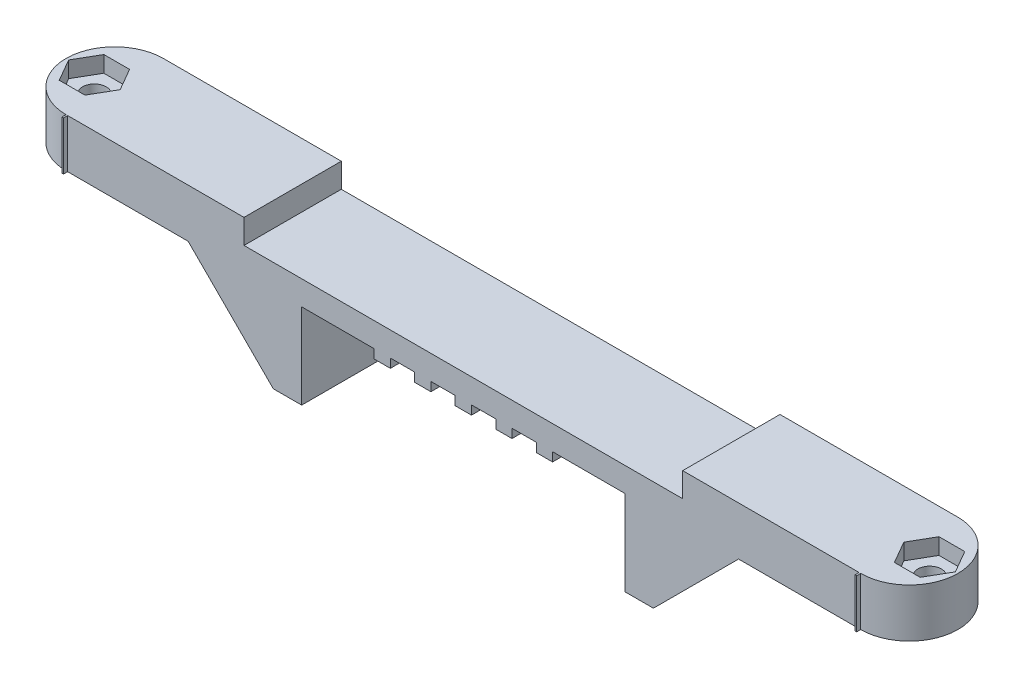
SolidWorks part; units mm, degrees
ref_plane "Front Plane" through (0, 0, 0) normal (0, 0, 1) x (1, 0, 0)
ref_plane "Top Plane" through (0, 0, 0) normal (0, 1, 0) x (1, 0, 0)
ref_plane "Right Plane" through (0, 0, 0) normal (1, 0, 0) x (0, 0, -1)
sketch "Sketch1" plane through (0, 0, 0) normal (0, 1, 0) x (1, 0, 0)
  line L0 (-49, 0) -> (49, 0) construction
  line L1 (-49, 6) -> (49, 6)
  line L2 (-49, -6) -> (49, -6)
  arc A0 (-49, 6) -> (-49, -6) centre (-49, 0) ccw
  arc A1 (49, -6) -> (49, 6) centre (49, 0) ccw
  circle A2 centre (-51.5, 0) radius 1.45
  circle A3 centre (51.5, 0) radius 1.45
  point P2 (0, 0)
  point P12 (-55, 0)
  point P13 (55, 0)
  dimension "D3" = 2.9
  dimension "D4" = 3.5
  dimension "D1" = 110
  dimension "D2" = 12
  dimension "D5" = 3.5
extrude "Boss-Extrude1" add sketch "Sketch1" along normal blind 3 contours L2 A1 L1 A0 | A2 | A3
sketch "Sketch4" plane through (0, 0, 0) normal (0, -1, 0) x (1, 0, 0)
  line L0 (-19.94, 6) -> (-19.94, -6)
  line L1 (-49, 6) -> (49, 6) construction
  line L2 (-49, -6) -> (49, -6) construction
  line L3 (-19.94, -6) -> (-23.44, -6)
  line L4 (-23.44, -6) -> (-23.44, 6)
  line L5 (-23.44, 6) -> (-19.94, 6)
  line L6 (0, 6) -> (0, -6) construction
  line L7 (-19.94, 5.075) -> (-19.94, -14.3256) construction
  line L8 (23.44, -6) -> (23.44, 6)
  line L9 (19.94, -6) -> (23.44, -6)
  line L10 (19.94, 6) -> (19.94, -6)
  line L11 (23.44, 6) -> (19.94, 6)
  dimension "D1" = 0
  dimension "D2" = 3.5
extrude "Boss-Extrude3" add sketch "Sketch4" along normal blind 10.5
sketch "Sketch5" plane through (0, 0, 0) normal (0, -1, 0) x (1, 0, 0)
  line L1 (4, 6) -> (4, -6)
  line L2 (4, 6) -> (6, 6)
  line L6 (-19.94, -6) -> (19.94, -6) construction
  line L7 (-1, 6) -> (1, 6)
  line L8 (-1, 6) -> (-1, -6)
  line L9 (-1, -6) -> (1, -6)
  line L10 (1, 6) -> (1, -6)
  line L11 (-1, 6) -> (1, -6) construction
  line L12 (-1, -6) -> (1, 6) construction
  line L13 (6, 6) -> (6, -6)
  line L14 (4, -6) -> (6, -6)
  line L15 (9, 6) -> (9, -6)
  line L16 (9, 6) -> (11, 6)
  line L17 (11, 6) -> (11, -6)
  line L18 (9, -6) -> (11, -6)
  line L19 (-4, 6) -> (-4, -6)
  line L20 (-6, -6) -> (-4, -6)
  line L21 (-6, 6) -> (-6, -6)
  line L22 (-6, 6) -> (-4, 6)
  line L23 (-9, 6) -> (-9, -6)
  line L24 (-11, -6) -> (-9, -6)
  line L25 (-11, 6) -> (-11, -6)
  line L26 (-11, 6) -> (-9, 6)
  point P0 (0, 0)
  dimension "D1" = 2
  dimension "D2" = 3
  dimension "D3" = 3
extrude "Boss-Extrude4" add sketch "Sketch5" along normal blind 1.1
sketch "Sketch6" plane through (0, 0, 6) normal (0, 0, 1) x (1, 0, 0)
  line L0 (49, 0) -> (49, 3)
  line L1 (49, 3) -> (48.8, 3)
  line L2 (-49, 3) -> (49, 3) construction
  line L3 (48.8, 3) -> (48.8, 0)
  line L4 (23.44, 0) -> (49, 0) construction
  line L5 (48.8, 0) -> (49, 0)
  line L6 (0, 0) -> (0, 3) construction
  line L7 (-48.8, 0) -> (-49, 0)
  line L8 (-48.8, 3) -> (-48.8, 0)
  line L9 (-49, 3) -> (-48.8, 3)
  line L10 (-49, 0) -> (-49, 3)
  dimension "D1" = 0.2
extrude "Boss-Extrude5" add sketch "Sketch6" along normal blind 0.5 contours L0 L1 L3 L5 | L8 L7 L10 L9
chamfer "Chamfer1" distance 10.5 2 edges at (23.44, 0, 0) (-23.44, 0, 0)
hole_wizard "Ø3.0mm Dowel Hole1" positions "Sketch7" profile "Sketch9" hole size "Ø3.0" standard "ANSI Metric" end condition up to next
sketch "Sketch7" plane through (0, 3, 0) normal (0, 1, 0) x (1, 0, 0)
  point P0 (-51.5, 0)
  point P2 (51.5, 0)
sketch "Sketch9" plane through (-51.5, 3, 0) normal (1, 0, 0) x (0, 0, 1)
  line L0 (0, 0) -> (0, 13.5)
  line L1 (0, 13.5) -> (1.45, 13.5)
  line L2 (1.45, 13.5) -> (1.45, 0)
  line L5 (1.45, 0) -> (0, 0)
  line L11 (0, -6.35) -> (0, 107.95) construction
  dimension "Thru Hole Dia." = 2.9
  dimension "Thru Hole Depth" = 13.5
sketch "Sketch10" plane through (0, 3, 0) normal (0, 1, 0) x (1, 0, 0)
  line L0 (-27.05, -6) -> (-27.05, 6)
  line L1 (27.05, -6) -> (27.05, 6)
  line L4 (27.05, -6) -> (48.8, -6)
  line L5 (-27.05, 6) -> (-49, 6)
  line L6 (-27, -44.4532) -> (-27, 21.84) construction
  line L8 (-49, -6) -> (-49, -6.5)
  line L9 (-49, -6.5) -> (-48.8, -6.5)
  line L10 (-48.8, -6.5) -> (-48.8, -6)
  line L11 (-48.8, -6) -> (48.8, -6)
  line L12 (48.8, -6) -> (48.8, -6.5)
  line L13 (48.8, -6.5) -> (49, -6.5)
  line L14 (49, -6.5) -> (49, -6)
  line L15 (49, 6) -> (-49, 6)
  line L16 (-49, -6) -> (-49, -6.5)
  line L17 (-49, -6.5) -> (-48.8, -6.5)
  line L18 (-48.8, -6.5) -> (-48.8, -6)
  line L19 (-48.8, -6) -> (-27.05, -6)
  line L20 (48.8, -6) -> (48.8, -6.5)
  line L21 (48.8, -6.5) -> (49, -6.5)
  line L22 (49, -6.5) -> (49, -6)
  line L23 (49, 6) -> (27.05, 6)
  line L24 (27, 21.84) -> (27, -44.4532) construction
  circle A1 centre (51.5, 0) radius 1.45
  arc A2 (-49, 6) -> (-49, -6) centre (-49, 0) ccw
  arc A3 (49, -6) -> (49, 6) centre (49, 0) ccw
  arc A4 (-49, 6) -> (-49, -6) centre (-49, 0) ccw
  arc A5 (49, -6) -> (49, 6) centre (49, 0) ccw
  circle A7 centre (-51.5, 0) radius 1.45
  circle A8 centre (51.5, 0) radius 1.45 construction
  line M20 (-48.8, -6) -> (48.8, -6)
  line M21 (48.8, -6) -> (48.8, -6.5)
  line M22 (48.8, -6.5) -> (49, -6.5)
  line M23 (49, -6.5) -> (49, -6)
  arc M24 (49, -6) -> (49, 6) centre (49, 0) ccw
  line M25 (49, 6) -> (-49, 6)
  circle M26 centre (51.5, 0) radius 1.45
  dimension "D4" = 2.9
  dimension "D5" = 2.9
  dimension "D2" = 0.05
  dimension "D3" = 0.05
  dimension "D1" = 0
extrude "Boss-Extrude6" add sketch "Sketch10" along normal blind 3 contours L1 M20 M21 M22 M23 M24 M25 M26 | A4 L16 L17 L18 L19 L0 L5 | A7 region at (40.1839, 3, 0.002)
sketch "Sketch11" plane through (0, 6, 0) normal (0, 1, 0) x (1, 0, 0)
  line L1 (-53.0877, 2.75) -> (-54.6754, 0)
  line L2 (-54.6754, 0) -> (-53.0877, -2.75)
  line L3 (-53.0877, -2.75) -> (-49.9123, -2.75)
  line L4 (-49.9123, -2.75) -> (-48.3246, 0)
  line L5 (-48.3246, 0) -> (-49.9123, 2.75)
  line L6 (-49.9123, 2.75) -> (-53.0877, 2.75)
  line L8 (-48.8, -6) -> (-27.05, -6) construction
  line L9 (0, 0) -> (0, -50000) construction
  line L10 (49.9123, 2.75) -> (53.0877, 2.75)
  line L11 (48.3246, 0) -> (49.9123, 2.75)
  line L12 (49.9123, -2.75) -> (48.3246, 0)
  line L13 (53.0877, -2.75) -> (49.9123, -2.75)
  line L14 (54.6754, 0) -> (53.0877, -2.75)
  line L15 (53.0877, 2.75) -> (54.6754, 0)
  circle A0 centre (-51.5, 0) radius 2.75 construction
  circle M15 centre (-51.5, 0) radius 1.45
  dimension "D1" = 5.5
extrude "Cut-Extrude1" cut sketch "Sketch11" against normal blind 2 contours L15 L10 L11 L12 L13 L14 | L5 L6 L1 L2 L3 L4 M15 region at (-51.5, 6, -2.666) region at (51.5, 6, 0)
